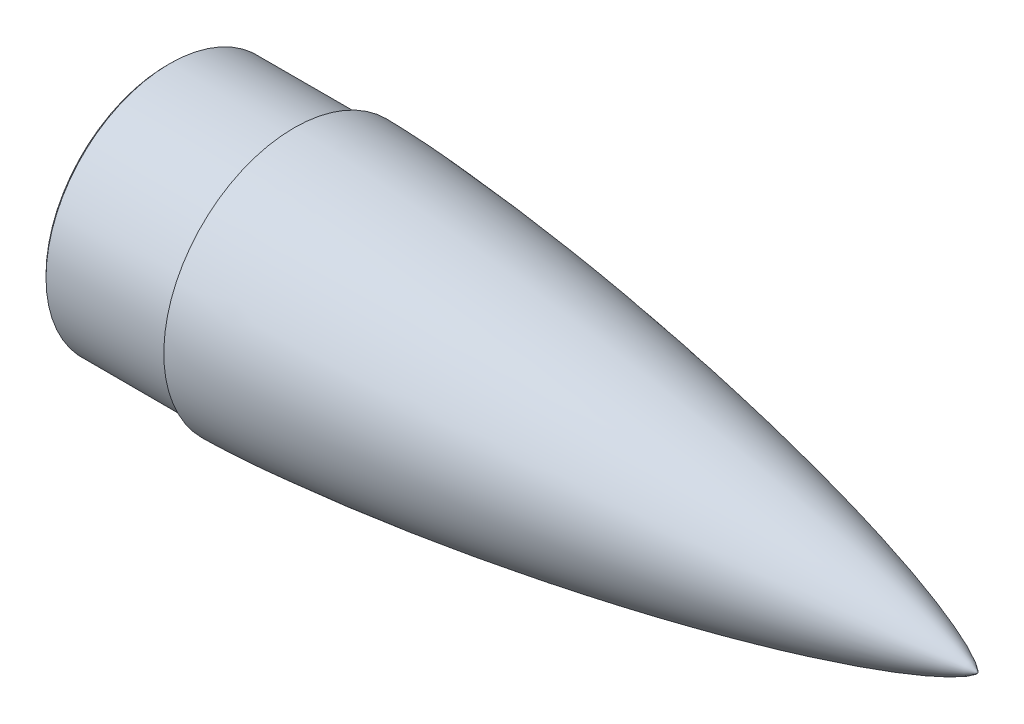
SolidWorks part; units mm, degrees
material "ABS"
ref_plane "Front Plane" through (0, 0, 0) normal (0, 0, 1) x (1, 0, 0)
ref_plane "Top Plane" through (0, 0, 0) normal (0, 1, 0) x (1, 0, 0)
ref_plane "Right Plane" through (0, 0, 0) normal (1, 0, 0) x (0, 0, -1)
ref_axis "Axis1" through (433.6458, 0, 0) along (-1, 0, 0)
sketch "Sketch10" plane through (0, 0, 0) normal (0, 0, 1) x (1, 0, 0)
  line L1 (0.7424, 0) -> (486.9547, 0) construction
  line L3 (10.5834, 71.2) -> (-75.8047, 71.2)
  line L4 (410.7424, 0) -> (370.7424, 0)
  line L5 (-75.8047, 71.2) -> (-75.8047, 74.2)
  line L6 (-75.8047, 74.2) -> (0.3953, 74.2)
  line L7 (0.3953, 74.2) -> (0.3953, 78.2)
  spline S0 degree 4 poles (410.7424, 0) (410.7398, 0.0134) (410.7324, 0.0397) (410.7098, 0.0898) (410.6637, 0.1724) (410.5956, 0.2725) (410.488, 0.4105) (410.3234, 0.5962) (410.0622, 0.858) (409.6177, 1.2514) (408.8561, 1.845) (407.519, 2.7573) (405.1467, 4.1679) (400.9623, 6.3231) (394.0504, 9.4024) (382.1295, 14.0164) (364.9778, 19.7328) (343.4154, 26.0357) (318.4835, 32.5226) (292.7983, 38.5792) (267.0037, 44.1504) (241.1221, 49.2999) (215.1671, 54.0652) (189.1485, 58.4693) (166.3323, 62.0155) (146.743, 64.8357) (130.3978, 67.0361) (117.3096, 68.7045) (104.2097, 70.2777) (92.7371, 71.5674) (82.8964, 72.6073) (74.691, 73.4278) (68.124, 74.0554) (61.5541, 74.653) (54.9814, 75.2189) (48.4059, 75.7512) (41.8276, 76.2478) (36.0691, 76.6486) (31.1315, 76.9656) (27.0157, 77.2107) (23.7224, 77.3945) (20.1036, 77.582) (16.7335, 77.7402) (13.6122, 77.8711) (10.7399, 77.977) (8.4417, 78.0517) (6.1431, 78.1158) (4.1316, 78.1598) (2.4073, 78.188) (1.2576, 78.1977) (0.6827, 78.2013) (0.3953, 78.2) knots 0 0 0 0 0 0.00013 0.00026 0.00052 0.0009 0.00128 0.001925 0.002882 0.004418 0.006927 0.011111 0.018279 0.030673 0.051704 0.083102 0.139909 0.202703 0.265496 0.32829 0.391083 0.453877 0.516671 0.579464 0.642258 0.673655 0.705051 0.736448 0.767845 0.799242 0.81494 0.830639 0.846337 0.862036 0.877734 0.893432 0.909131 0.924829 0.932678 0.940527 0.948377 0.956226 0.967169 0.972641 0.978113 0.983585 0.989056 0.994528 0.997264 1 1 1 1 1 construction
  spline S1 degree 4 poles (410.7424, 0) (410.7398, 0.0134) (410.7324, 0.0397) (410.7098, 0.0898) (410.6637, 0.1724) (410.5956, 0.2725) (410.488, 0.4105) (410.3234, 0.5962) (410.0622, 0.858) (409.6177, 1.2514) (408.8561, 1.845) (407.519, 2.7573) (405.1467, 4.1679) (400.9623, 6.3231) (394.0504, 9.4024) (382.1295, 14.0164) (364.9778, 19.7328) (343.4154, 26.0357) (318.4835, 32.5226) (292.7983, 38.5792) (267.0037, 44.1504) (241.1221, 49.2999) (215.1671, 54.0652) (189.1485, 58.4693) (166.3323, 62.0155) (146.743, 64.8357) (130.3978, 67.0361) (117.3096, 68.7045) (104.2097, 70.2777) (92.7371, 71.5674) (82.8964, 72.6073) (74.691, 73.4278) (68.124, 74.0554) (61.5541, 74.653) (54.9814, 75.2189) (48.4059, 75.7512) (41.8276, 76.2478) (36.0691, 76.6486) (31.1315, 76.9656) (27.0157, 77.2107) (23.7224, 77.3945) (20.1036, 77.582) (16.7335, 77.7402) (13.6122, 77.8711) (10.7399, 77.977) (8.4417, 78.0517) (6.1431, 78.1158) (4.1316, 78.1598) (2.4073, 78.188) (1.2576, 78.1977) (0.6827, 78.2013) (0.3953, 78.2) knots 0 0 0 0 0 0.00013 0.00026 0.00052 0.0009 0.00128 0.001925 0.002882 0.004418 0.006927 0.011111 0.018279 0.030673 0.051704 0.083102 0.139909 0.202703 0.265496 0.32829 0.391083 0.453877 0.516671 0.579464 0.642258 0.673655 0.705051 0.736448 0.767845 0.799242 0.81494 0.830639 0.846337 0.862036 0.877734 0.893432 0.909131 0.924829 0.932678 0.940527 0.948377 0.956226 0.967169 0.972641 0.978113 0.983585 0.989056 0.994528 0.997264 1 1 1 1 1
  spline S2 degree 4 poles (370.7424, 0) (370.7401, 0.0123) (370.7335, 0.0363) (370.7133, 0.0821) (370.6727, 0.1567) (370.6132, 0.2465) (370.5196, 0.37) (370.3755, 0.5376) (370.1445, 0.7759) (369.7492, 1.1355) (369.0686, 1.6803) (367.8743, 2.5164) (365.7511, 3.8116) (362.0233, 5.7811) (355.9127, 8.5762) (345.4232, 12.752) (330.3699, 17.9224) (311.463, 23.6264) (289.5923, 29.5064) (267.0541, 35.0035) (244.4144, 40.0656) (221.6939, 44.7495) (198.905, 49.0886) (176.0569, 53.103) (156.0182, 56.3392) (138.8116, 58.9157) (124.4535, 60.9279) (112.9556, 62.4548) (101.4467, 63.896) (91.3669, 65.0787) (82.7204, 66.0333) (75.5105, 66.7872) (69.7399, 67.3643) (63.9666, 67.9143) (58.1907, 68.4357) (52.4121, 68.9267) (46.6309, 69.3854) (41.57, 69.7561) (37.2304, 70.0499) (33.613, 70.2774) (30.7183, 70.4482) (27.5607, 70.6215) (24.14, 70.792) (20.9491, 70.9314) (17.9883, 71.0405) (15.5205, 71.1156) (13.7927, 71.1578) (12.3116, 71.1857) (11.324, 71.1964) (10.8303, 71.2005) (10.5834, 71.2) knots 0 0 0 0 0 0.000135 0.00027 0.00054 0.00092 0.001299 0.001947 0.002931 0.004512 0.007081 0.01138 0.018708 0.031424 0.052705 0.084103 0.14091 0.203703 0.266497 0.329291 0.392084 0.454878 0.517672 0.580465 0.643259 0.674656 0.706052 0.737449 0.768846 0.800243 0.815941 0.831639 0.847338 0.863036 0.878735 0.894433 0.910132 0.92583 0.933679 0.941528 0.949378 0.957227 0.96792 0.978613 0.98396 0.989307 0.994653 0.997327 1 1 1 1 1 construction
  spline S3 degree 4 poles (370.7424, 0) (370.7401, 0.0123) (370.7335, 0.0363) (370.7133, 0.0821) (370.6727, 0.1567) (370.6132, 0.2465) (370.5196, 0.37) (370.3755, 0.5376) (370.1445, 0.7759) (369.7492, 1.1355) (369.0686, 1.6803) (367.8743, 2.5164) (365.7511, 3.8116) (362.0233, 5.7811) (355.9127, 8.5762) (345.4232, 12.752) (330.3699, 17.9224) (311.463, 23.6264) (289.5923, 29.5064) (267.0541, 35.0035) (244.4144, 40.0656) (221.6939, 44.7495) (198.905, 49.0886) (176.0569, 53.103) (156.0182, 56.3392) (138.8116, 58.9157) (124.4535, 60.9279) (112.9556, 62.4548) (101.4467, 63.896) (91.3669, 65.0787) (82.7204, 66.0333) (75.5105, 66.7872) (69.7399, 67.3643) (63.9666, 67.9143) (58.1907, 68.4357) (52.4121, 68.9267) (46.6309, 69.3854) (41.57, 69.7561) (37.2304, 70.0499) (33.613, 70.2774) (30.7183, 70.4482) (27.5607, 70.6215) (24.14, 70.792) (20.9491, 70.9314) (17.9883, 71.0405) (15.5205, 71.1156) (13.7927, 71.1578) (12.3116, 71.1857) (11.324, 71.1964) (10.8303, 71.2005) (10.5834, 71.2) knots 0 0 0 0 0 0.000135 0.00027 0.00054 0.00092 0.001299 0.001947 0.002931 0.004512 0.007081 0.01138 0.018708 0.031424 0.052705 0.084103 0.14091 0.203703 0.266497 0.329291 0.392084 0.454878 0.517672 0.580465 0.643259 0.674656 0.706052 0.737449 0.768846 0.800243 0.815941 0.831639 0.847338 0.863036 0.878735 0.894433 0.910132 0.92583 0.933679 0.941528 0.949378 0.957227 0.96792 0.978613 0.98396 0.989307 0.994653 0.997327 1 1 1 1 1
  dimension "D4" = 74.2
  dimension "D1" = 78.2
  dimension "D3" = 410
  dimension "D5" = 370
  dimension "D6" = 76.2
  dimension "D2" = 3
revolve "Revolve1" add sketch "Sketch10" angle 360 about axis through (433.6458, 0, 0) along (-1, 0, 0)
chamfer "Chamfer1" distance 1.5 angle 45 1 edges at (-75.8047, 0, -74.2)
equation "\"TubeDiameter\" = 6.000in"
equation "\"D1@Sketch10\"=(\"TubeDiameter\"/2)+2mm"
equation "\"D6@Sketch10\"=\"TubeDiameter\"/2"
equation "\"D4@Sketch10\"=\"TubeDiameter\"/2-2mm"
